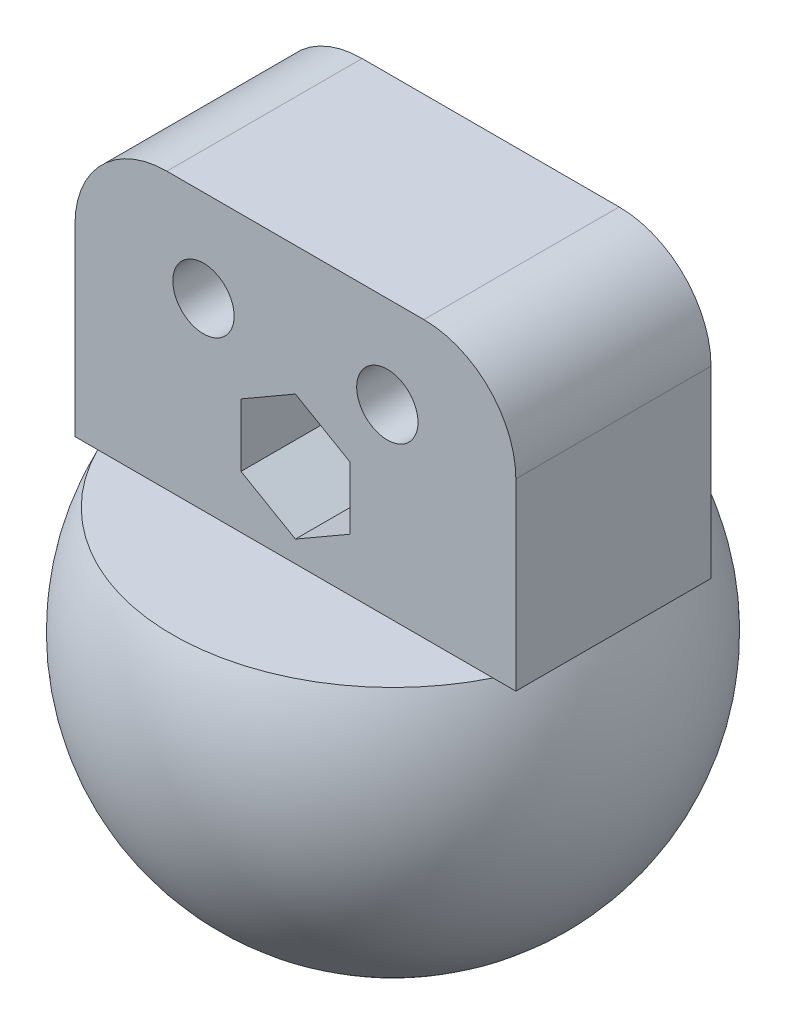
SolidWorks part; units mm, degrees
ref_plane "Front Plane" through (0, 0, 0) normal (0, 0, 1) x (1, 0, 0)
ref_plane "Top Plane" through (0, 0, 0) normal (0, 1, 0) x (1, 0, 0)
ref_plane "Right Plane" through (0, 0, 0) normal (1, 0, 0) x (0, 0, -1)
sketch "Sketch1" plane through (0, 0, 0) normal (0, 0, 1) x (1, 0, 0)
  line L0 (0, 16) -> (0, -16)
  arc A0 (0, -16) -> (0, 16) centre (0, 0) ccw
  dimension "D1" = 16
revolve "Revolve1" add sketch "Sketch1" angle 360 about L0
sketch "Sketch2" plane through (0, 0, 0) normal (0, 0, 1) x (1, 0, 0)
  line L0 (0, 0) -> (0, 25) construction
  line L1 (-14.3875, 25) -> (14.3875, 25)
  line L2 (-14.3875, 25) -> (-14.3875, 7)
  line L3 (-14.3875, 7) -> (14.3875, 7)
  line L4 (14.3875, 25) -> (14.3875, 7)
  line L5 (-6, 19) -> (6, 19) construction
  line L7 (0, 16.5992) -> (-3.55, 14.5496)
  line L8 (-3.55, 14.5496) -> (-3.55, 10.4504)
  line L9 (-3.55, 10.4504) -> (0, 8.4008)
  line L10 (0, 8.4008) -> (3.55, 10.4504)
  line L11 (3.55, 10.4504) -> (3.55, 14.5496)
  line L12 (3.55, 14.5496) -> (0, 16.5992)
  circle A0 centre (0, 0) radius 16 construction
  circle A1 centre (-6, 19) radius 2
  circle A2 centre (6, 19) radius 2
  circle A3 centre (0, 12.5) radius 3.55 construction
  point P13 (0, 19)
  dimension "D3" = 4
  dimension "D1" = 7
  dimension "D2" = 18
  dimension "D4" = 19
  dimension "D5" = 12
  dimension "D6" = 4.0992
  dimension "D7" = 3.55
extrude "Boss-Extrude1" add sketch "Sketch2" along normal mid plane 12.74
sketch "Sketch3" plane through (0, 0, 6.37) normal (0, 0, 1) x (1, 0, 0)
  line L1 (-14.3875, 25) -> (12.9005, 25)
  line L2 (-14.3875, 25) -> (-14.3875, 7)
  line L3 (-14.3875, 7) -> (12.9005, 7)
  line L4 (12.9005, 25) -> (12.9005, 7)
extrude "Cut-Extrude1" cut sketch "Sketch3" along normal up to next
extrude "Cut-Extrude2" cut sketch "Sketch2<2>" against normal up to next from surface contours L11 L12 L7 L8 L9 L10 | L4 L1 L2 L3 A2 A1 L12 L11 L10 L9 L8 L7 region at (0, 24.6606, 0) region at (0, 12.5, 0) starting at face at (-4, 19, -6.37)
sketch "Sketch2<2>" plane through (0, 0, 0) normal (0, 0, 1) x (1, 0, 0) same geometry as "Sketch2"
fillet "Fillet1" radius 6 2 edges at (-14.3875, 25, 0) (14.3875, 25, 0)
extrude "Cut-Extrude3" cut sketch "Sketch2<3>" against normal through all both and the other way through all contours L8 L9 L10 L11 L12 L7
sketch "Sketch2<3>" plane through (0, 0, 0) normal (0, 0, 1) x (1, 0, 0) same geometry as "Sketch2"
